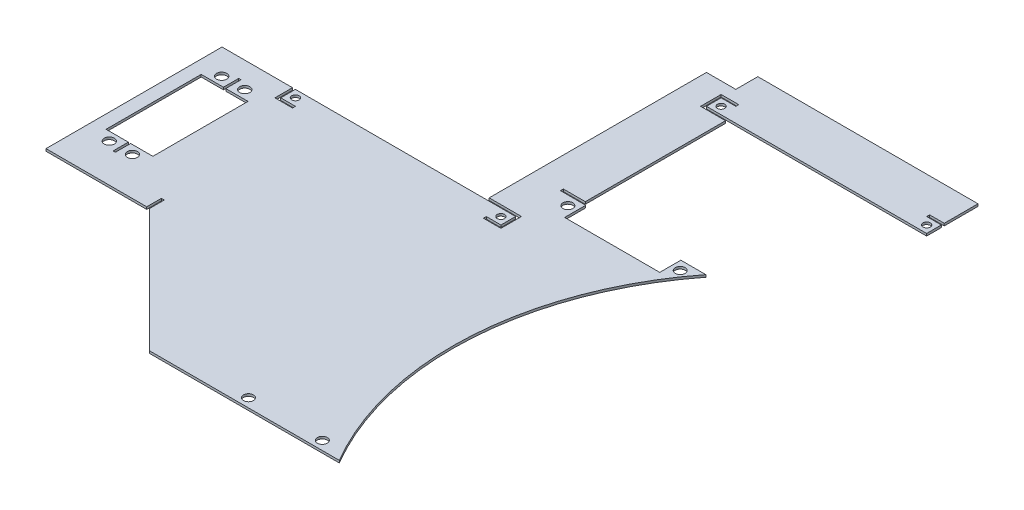
SolidWorks part; units mm, degrees
ref_plane "Front Plane" through (0, 0, 0) normal (0, 0, 1) x (1, 0, 0)
ref_plane "Top Plane" through (0, 0, 0) normal (0, 1, 0) x (1, 0, 0)
ref_plane "Right Plane" through (0, 0, 0) normal (1, 0, 0) x (0, 0, -1)
sketch "Sketch2" plane through (0, 0, 0) normal (0, 1, 0) x (1, 0, 0)
  line L1 (-127, -127) -> (127, -127)
  line L2 (-127, -127) -> (-127, 127)
  line L3 (-127, 127) -> (127, 127)
  line L4 (127, -127) -> (127, 127)
  line L5 (-127, -127) -> (127, 127) construction
  line L6 (-127, 127) -> (127, -127) construction
  point P0 (0, 0)
  dimension "D1" = 254
  dimension "D2" = 254
extrude "Boss-Extrude1" add sketch "Sketch2" along normal blind 1.0008 contours L3 L4 L1 L2
sketch "Sketch3" plane through (0, 1.0008, 0) normal (0, 1, 0) x (1, 0, 0)
  line L0 (63.5, 41.91) -> (63.5, 3.81) construction
  line L1 (127, 47.252) -> (57.15, 47.252)
  line L2 (127, 47.252) -> (127, 21.852)
  line L3 (127, 21.852) -> (57.15, 21.852)
  line L4 (57.15, 47.252) -> (57.15, 21.852)
  line L7 (64.096, 22.36) -> (70.7, 22.36) construction
  line L8 (64.096, 22.36) -> (70.7, 22.36) construction
  dimension "D1" = 6.35
  dimension "D2" = 0.508
  dimension "D3" = 25.4
extrude "Cut-Extrude1" cut sketch "Sketch3" against normal through all both and the other way through all
sketch "Sketch4" plane through (0, 1.0008, 0) normal (0, 1, 0) x (1, 0, 0)
  line L6 (127, -127) -> (127, 21.852)
  line L8 (127, 21.852) -> (57.15, 21.852)
  line L9 (127, 127) -> (-127, 127)
  line L10 (-127, 127) -> (-127, -127)
  line L11 (-127, -127) -> (127, -127)
  line L12 (127, -127) -> (127, 21.852)
  line L17 (112.9689, -127) -> (127, -127)
  line L18 (127, 21.852) -> (122.64, 21.852)
  line L19 (57.15, 21.852) -> (57.15, 47.252)
  line L22 (57.15, 47.252) -> (127, 47.252)
  line L24 (127, 47.252) -> (127, 127)
  arc A0 (127, 27.1603) -> (114.5024, -129.54) centre (227.33, -59.69) ccw construction
  arc A1 (122.64, 21.852) -> (112.9689, -127) centre (227.33, -59.69) ccw
  dimension "D1" = 0
extrude "Cut-Extrude2" cut sketch "Sketch4" against normal through all both
sketch "Sketch5" plane through (0, 1.0008, 0) normal (0, 1, 0) x (1, 0, 0)
  line L0 (63.5, -129.54) -> (63.5, -61.2891) construction
  circle A0 centre (115.577, 17.86) radius 2.1 construction
  circle A1 centre (66.977, 17.86) radius 2.1 construction
  circle A2 centre (115.577, 17.86) radius 2.1 construction
  circle A3 centre (66.977, 17.86) radius 2.1 construction
  circle A4 centre (69.85, -123.19) radius 2.15
  circle A5 centre (101.8024, -123.19) radius 2.15
  circle A6 centre (66.977, 17.86) radius 2.15
  circle A7 centre (115.577, 17.86) radius 2.15
  dimension "D1" = 6.35
  dimension "D5" = 4.3
  dimension "D2" = 12.7
  dimension "D3" = 6.35
  dimension "D4" = 6.35
extrude "Cut-Extrude3" cut sketch "Sketch5" against normal through all both
sketch "Sketch6" plane through (0, 1.0008, 0) normal (0, 1, 0) x (1, 0, 0)
  line L12 (70.7, 22.36) -> (70.7, 12.733)
  line L13 (70.7, 12.733) -> (111.854, 12.733)
  line L14 (111.854, 12.733) -> (111.854, 22.36)
  line L15 (111.854, 22.36) -> (118.458, 22.36)
  line L16 (118.458, 22.36) -> (118.458, 23.36)
  line L17 (118.458, 23.36) -> (111.854, 23.36)
  line L18 (111.854, 23.36) -> (111.854, 32.987)
  line L19 (111.854, 32.987) -> (70.7, 32.987)
  line L20 (70.7, 32.987) -> (70.7, 23.36)
  line L21 (70.7, 23.36) -> (64.096, 23.36)
  line L22 (64.096, 23.36) -> (64.096, 22.36)
  line L23 (64.096, 22.36) -> (70.7, 22.36)
  line L24 (70.7, 22.36) -> (70.7, 12.733)
  line L25 (70.7, 12.733) -> (111.854, 12.733)
  line L26 (111.854, 12.733) -> (111.854, 22.36)
  line L27 (111.854, 22.36) -> (118.458, 22.36)
  line L28 (118.458, 22.36) -> (118.458, 23.36)
  line L29 (118.458, 23.36) -> (111.854, 23.36)
  line L30 (111.854, 23.36) -> (111.854, 32.987)
  line L31 (111.854, 32.987) -> (70.7, 32.987)
  line L32 (70.7, 32.987) -> (70.7, 23.36)
  line L33 (70.7, 23.36) -> (64.096, 23.36)
  line L34 (64.096, 23.36) -> (64.096, 22.36)
  line L35 (64.096, 22.36) -> (70.7, 22.36)
  circle A1 centre (66.977, 27.86) radius 2.1
  circle A2 centre (66.977, 27.86) radius 2.1
  circle A3 centre (66.977, 17.86) radius 2.1
  circle A4 centre (66.977, 17.86) radius 2.1
  circle A5 centre (115.577, 27.86) radius 2.1
  circle A6 centre (115.577, 27.86) radius 2.1
  circle A7 centre (115.577, 17.86) radius 2.1
  circle A8 centre (115.577, 17.86) radius 2.1
  dimension "D1" = 0
  dimension "D2" = 0
  dimension "D3" = 0
  dimension "D4" = 0
  dimension "D5" = 0
extrude "Cut-Extrude4" cut sketch "Sketch6" against normal through all both
sketch "Sketch7" plane through (0, 1.0008, 0) normal (0, 1, 0) x (1, 0, 0)
  line L1 (-35.5092, 2.4892) -> (59.7408, 2.4892)
  line L2 (-35.5092, 2.4892) -> (-35.5092, 97.7392)
  line L3 (-35.5092, 97.7392) -> (59.7408, 97.7392)
  line L4 (59.7408, 2.4892) -> (59.7408, 97.7392)
  line L5 (-35.5092, 2.4892) -> (59.7408, 97.7392) construction
  line L6 (-35.5092, 97.7392) -> (59.7408, 2.4892) construction
  circle A2 centre (101.6, 22.86) radius 4.7625 construction
  circle A3 centre (101.6, 22.86) radius 4.699 construction
  point P0 (12.1158, 50.1142)
  dimension "D1" = 95.25
  dimension "D3" = 20.3708
  dimension "D2" = 137.1092
extrude "Cut-Extrude5" cut sketch "Sketch7" against normal through all both
sketch "Sketch8" plane through (0, 1.0008, 0) normal (0, 1, 0) x (1, 0, 0)
  line L0 (127, 47.252) -> (127, 127)
  line L2 (127, 127) -> (-127, 127)
  line L3 (-127, 127) -> (-127, -127)
  line L4 (-127, -127) -> (-35.5092, -127)
  line L5 (-127, -127) -> (112.9689, -127) construction
  line L6 (-35.5092, -127) -> (-35.5092, 47.252)
  line L7 (-35.5092, 47.252) -> (127, 47.252)
  line L9 (-35.5092, 97.7392) -> (-35.5092, 2.4892) construction
extrude "Cut-Extrude6" cut sketch "Sketch8" against normal through all both
sketch "Sketch17" plane through (0, 1.0008, 0) normal (0, 1, 0) x (1, 0, 0)
  line L1 (59.7408, 2.4892) -> (47.0408, 2.4892)
  line L2 (59.7408, 2.4892) -> (59.7408, 85.0392)
  line L3 (59.7408, 97.7392) -> (47.0408, 97.7392)
  line L4 (47.0408, 2.4892) -> (47.0408, 97.7392)
  line L5 (-35.5092, 2.4892) -> (59.7408, 2.4892) construction
  line L6 (59.7408, 97.7392) -> (154.9908, 97.7392)
  line L8 (59.7408, 85.0392) -> (154.9908, 85.0392)
  line L9 (154.9908, 97.7392) -> (154.9908, 85.0392)
  dimension "D1" = 12.7
extrude "Boss-Extrude4" add sketch "Sketch17" against normal up to surface (1.0008 mm away) up to face at (62.6286, 0, 13.466)
sketch "Sketch18" plane through (0, 1.0008, 0) normal (0, 1, 0) x (1, 0, 0)
  line L0 (47.0408, 2.4892) -> (59.7408, 2.4892)
extrude "Cut-Extrude-Thin4" cut sketch "Sketch18" against normal through all both and the other way through all thin thin type one direction reverse wall 1.27
sketch "Sketch9" plane through (0, 1.0008, 0) normal (0, 1, 0) x (1, 0, 0)
  line L0 (-35.5092, -60.5651) -> (30.9257, -127)
  line L1 (-35.5092, -127) -> (-35.5092, 2.4892) construction
  line L2 (-35.5092, -127) -> (112.9689, -127) construction
  line L3 (-35.5092, -127) -> (30.9257, -127)
  line L4 (-35.5092, -127) -> (-35.5092, -60.5651)
  circle A0 centre (101.727, 22.86) radius 149.6811 construction
  circle A1 centre (101.727, 22.86) radius 156.0311 construction
  dimension "D1" = 6.35
  dimension "D2" = 45
extrude "Cut-Extrude7" cut sketch "Sketch9" against normal through all both
sketch "Sketch10" plane through (0, 1.0008, 0) normal (0, 1, 0) x (1, 0, 0)
  line L37 (59.7408, 21.852) -> (59.7408, 85.0392) construction
  line L38 (59.7408, 83.7692) -> (69.2658, 83.7692)
  line L39 (59.7408, 83.7692) -> (59.7408, 23.122)
  line L40 (59.7408, 23.122) -> (69.2658, 23.122)
  line L41 (69.2658, 83.7692) -> (69.2658, 23.122)
  line L42 (70.7, 21.852) -> (59.7408, 21.852) construction
  line L43 (59.7408, 85.0392) -> (154.9908, 85.0392) construction
  line L44 (154.9908, 97.7392) -> (47.0408, 97.7392) construction
  line L45 (59.7408, 97.7392) -> (154.9908, 97.7392)
  line L46 (59.7408, 97.7392) -> (59.7408, 107.2642)
  line L47 (59.7408, 107.2642) -> (154.9908, 107.2642)
  line L48 (154.9908, 97.7392) -> (154.9908, 107.2642)
  line M23 (-35.5092, -60.5651) -> (30.9257, -127)
  line M24 (30.9257, -127) -> (112.9689, -127)
  line M33 (-35.5092, 2.4892) -> (-35.5092, -60.5651)
  dimension "D1" = 1.27
  dimension "D2" = 1.27
  dimension "D3" = 9.525
extrude "Boss-Extrude2" add sketch "Sketch10" against normal up to surface (1.0008 mm away) contours M23 | M24 | M33 | L46 L45 L48 L47 | L39 L38 L41 L40 up to face at (69.4562, 0, -10.4618)
sketch "Sketch14" plane through (0, 1.0008, 0) normal (0, 1, 0) x (1, 0, 0)
  line L0 (-61.5112, -12.271) -> (-41.2572, -53.425) construction
  line L5 (-61.5112, -12.271) -> (-51.8842, -12.271)
  line L6 (-61.5112, -12.271) -> (-61.5112, -53.425)
  line L7 (-61.5112, -53.425) -> (-51.8842, -53.425)
  line L12 (-41.2572, -12.271) -> (-41.2572, -53.425)
  line L17 (-35.5092, -5.1308) -> (-67.2592, -5.1308)
  line L22 (-35.5092, -60.5651) -> (-35.5092, 2.4892) construction
  line L23 (-67.2592, -5.1308) -> (-67.2592, -60.5651)
  line L24 (-67.2592, -60.5651) -> (-35.5092, -60.5651)
  line L25 (-35.5092, -60.5651) -> (-35.5092, -5.1308)
  line L34 (-41.2572, -12.271) -> (-61.5112, -53.425) construction
  line L35 (-56.3842, -8.548) -> (-46.3842, -57.148) construction
  line L36 (-56.3842, -57.148) -> (-46.3842, -8.548) construction
  line L37 (-50.8842, -53.425) -> (-41.2572, -53.425)
  line L38 (-51.8842, -53.425) -> (-51.8842, -60.029)
  line L39 (-51.8842, -60.029) -> (-50.8842, -60.029)
  line L40 (-50.8842, -53.425) -> (-50.8842, -60.029)
  line L41 (-51.3842, -32.848) -> (-15.6253, -32.848) construction
  line L42 (-51.8842, -5.667) -> (-50.8842, -5.667)
  line L43 (-51.8842, -12.271) -> (-51.8842, -5.667)
  line L44 (-50.8842, -12.271) -> (-50.8842, -5.667)
  line L45 (-50.8842, -12.271) -> (-41.2572, -12.271)
  line L47 (-67.2592, -5.1308) -> (-67.2592, 2.4892)
  line L48 (-67.2592, 2.4892) -> (-35.5092, 2.4892)
  line L49 (-35.5092, 2.4892) -> (-35.5092, -5.1308)
  line L51 (-35.5092, 2.4892) -> (59.7408, 2.4892) construction
  line L52 (-67.2592, -60.5651) -> (-67.2592, -73.66)
  line L53 (-67.2592, -73.66) -> (-22.4143, -73.66)
  line L54 (30.9257, -127) -> (-35.5092, -60.5651) construction
  line L57 (-22.4143, -73.66) -> (-35.5092, -60.5651)
  circle A8 centre (-56.3842, -57.148) radius 2.2
  circle A9 centre (-46.3842, -57.148) radius 2.2
  circle A10 centre (-56.3842, -8.548) radius 2.2
  circle A11 centre (-46.3842, -8.548) radius 2.2
  point P9 (-51.3842, -60.029)
  point P19 (-51.3842, -32.848)
  point P20 (-51.3842, -32.848)
  point P37 (-67.2592, -32.848)
  point P39 (-51.3842, -60.5651)
  dimension "D3" = 48.6
  dimension "D4" = 4.4
  dimension "D2" = 10
  dimension "D5" = 41.154
  dimension "D6" = 20.254
  dimension "D7" = 1
  dimension "D8" = 6.604
  dimension "D9" = 31.75
  dimension "D10" = 7.62
  dimension "D11" = 53.34
extrude "Boss-Extrude3" add sketch "Sketch14" against normal up to surface (1.0008 mm away) contours L49 L48 L47 L17 | L24 L25 L17 L23 A11 A10 A9 A8 L44 L45 L12 L37 L40 L39 L38 L7 L6 L5 L43 L42 | L24 region at (-36.148, 1.0008, 32.848) region at (-51.3842, 1.0008, 1.3208) region at (-47.9239, 1.0008, 67.4857) up to face at (67.75, 0, -26.3548)
sketch "Sketch15" plane through (0, 1.0008, 0) normal (0, 1, 0) x (1, 0, 0)
  line L0 (-22.4143, -73.66) -> (-22.4143, -67.31)
  dimension "D1" = 6.35
extrude "Cut-Extrude-Thin3" cut sketch "Sketch15" against normal through all both and the other way through all thin thin type one direction reverse wall 1.27
sketch "Sketch19" plane through (0, 1.0008, 0) normal (0, 1, 0) x (1, 0, 0)
  line L0 (154.9908, 85.0392) -> (154.9908, 107.2642) construction
  line L1 (59.7408, 85.0392) -> (154.9908, 85.0392) construction
  line L2 (59.7408, 83.7692) -> (59.7408, 85.0392) construction
  line L3 (-67.2592, 2.4892) -> (59.7408, 2.4892) construction
  line L4 (59.7408, 2.4892) -> (59.7408, 3.7592) construction
  line L5 (62.9158, 88.2142) -> (151.8158, 88.2142) construction
  line L6 (-32.3342, -0.6858) -> (56.5658, -0.6858) construction
  circle A0 centre (56.5658, -0.6858) radius 1.5875
  circle A1 centre (-32.3342, -0.6858) radius 1.5875
  circle A2 centre (151.8158, 88.2142) radius 1.5875
  circle A3 centre (62.9158, 88.2142) radius 1.5875
  dimension "D3" = 3.175
  dimension "D1" = 3.175
  dimension "D2" = 3.175
  dimension "D4" = 3.175
  dimension "D5" = 3.175
  dimension "D6" = 3.175
extrude "Cut-Extrude8" cut sketch "Sketch19" against normal through all both and the other way through all
sketch "Sketch20" plane through (0, 1.0008, 0) normal (0, 1, 0) x (1, 0, 0)
  line L0 (-35.5092, 2.4892) -> (-35.5092, -3.8608)
  line L1 (-67.2592, 2.4892) -> (59.7408, 2.4892) construction
  line L2 (-35.5092, -3.8608) -> (-29.1592, -3.8608)
  line L3 (59.7408, 2.4892) -> (59.7408, -3.8608)
  line L4 (59.7408, -3.8608) -> (53.3908, -3.8608)
  line L5 (59.7408, 85.0392) -> (59.7408, 91.3892)
  line L6 (59.7408, 91.3892) -> (66.0908, 91.3892)
  line L7 (154.9908, 91.3892) -> (154.9908, 85.0392) construction
  line L8 (148.6408, 91.3892) -> (154.9908, 91.3892)
  line L9 (154.9908, 85.0392) -> (154.9908, 107.2642) construction
  line L10 (58.4708, 85.0392) -> (58.4708, 92.6592)
  line L11 (58.4708, 92.6592) -> (66.0908, 92.6592)
  line L12 (148.6408, 92.6592) -> (154.9908, 92.6592)
  line L13 (61.0108, 2.4892) -> (61.0108, -5.1308)
  line L14 (61.0108, -5.1308) -> (53.3908, -5.1308)
  line L15 (-36.7792, 2.4892) -> (-36.7792, -5.1308)
  line L16 (-36.7792, -5.1308) -> (-29.1592, -5.1308)
  line L17 (-36.7792, 2.4892) -> (-35.5092, 2.4892)
  line L18 (-29.1592, -3.8608) -> (-29.1592, -5.1308)
  line L19 (148.6408, 92.6592) -> (148.6408, 91.3892)
  line L20 (154.9908, 91.3892) -> (154.9908, 92.6592)
  line L21 (59.7408, 85.0392) -> (58.4708, 85.0392)
  line L22 (66.0908, 91.3892) -> (66.0908, 92.6592)
  line L23 (59.7408, 2.4892) -> (61.0108, 2.4892)
  line L24 (53.3908, -3.8608) -> (53.3908, -5.1308)
  line L25 (59.7408, 85.0392) -> (59.7408, 83.7692)
  line L26 (59.7408, 83.7692) -> (69.2658, 83.7692) construction
  line L27 (59.7408, 83.7692) -> (58.4708, 83.7692)
  line L28 (58.4708, 83.7692) -> (58.4708, 85.0392)
  line L29 (59.7408, 2.4892) -> (59.7408, 3.7592)
  line L30 (59.7408, 3.7592) -> (61.0108, 3.7592)
  line L31 (61.0108, 3.7592) -> (61.0108, 2.4892)
  dimension "D1" = 6.35
  dimension "D2" = 95.25
  dimension "D3" = 1.27
  dimension "D4" = 1.27
extrude "Cut-Extrude12" cut sketch "Sketch20" against normal through all both contours L28 L27 L25 L21 | L6 L22 L11 L10 L21 L5 | L31 L30 L29 L23 | L4 L24 L14 L13 L23 L3 | L18 L2 L0 L17 L15 L16 | L8 L20 L12 L19 region at (-35.617, 1.0008, 0.6858) region at (60.3758, 1.0008, -2.3814) region at (60.3758, 1.0008, -3.1242) region at (59.1058, 1.0008, -85.147) region at (59.1058, 1.0008, -84.4042)
equation "\"looseTol\"= 0.02in"
equation "\"tightTol\"= 0.005in"
equation "\"normTol\"= 0.01in"
equation "\"D2@Sketch3\"=\"looseTol\""
equation "\"D5@Sketch5\"=4.3mm"
